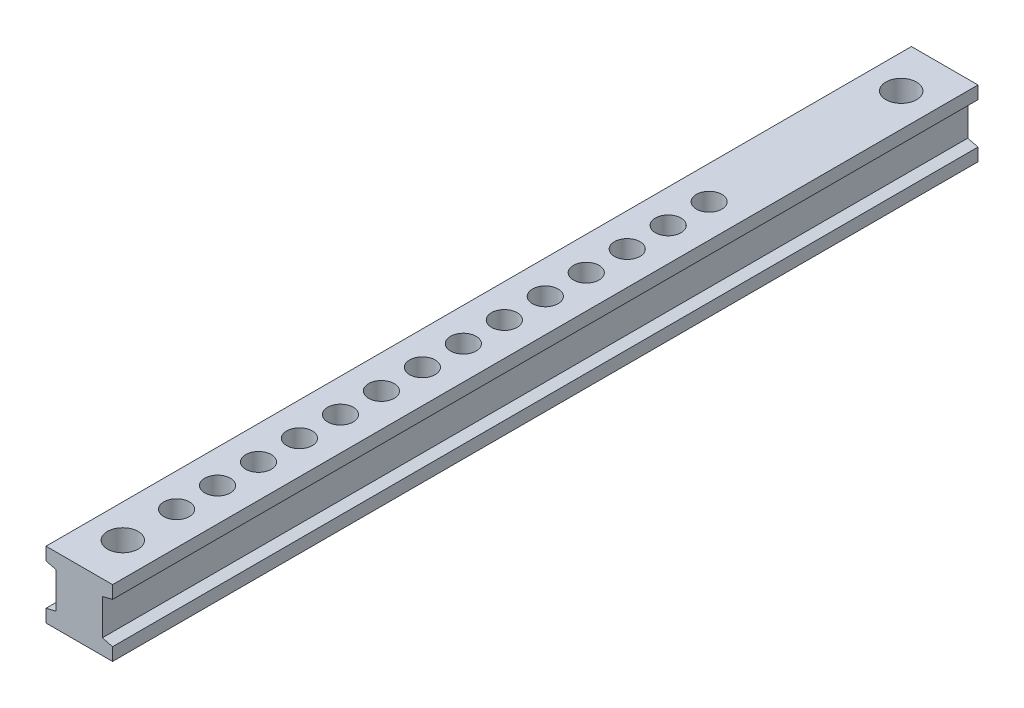
SolidWorks part; units mm, degrees
ref_plane "Front Plane" through (0, 0, 0) normal (0, 0, 1) x (1, 0, 0)
ref_plane "Top Plane" through (0, 0, 0) normal (0, 1, 0) x (1, 0, 0)
ref_plane "Right Plane" through (0, 0, 0) normal (1, 0, 0) x (0, 0, -1)
sketch "Sketch1" plane through (0, 0, 0) normal (0, 0, 1) x (1, 0, 0)
  line L0 (6.5, 4) -> (4.5, 3.5)
  line L1 (-6.5, 6.5) -> (6.5, 6.5)
  line L2 (-6.5, 6.5) -> (-6.5, -6.5)
  line L3 (-6.5, -6.5) -> (6.5, -6.5)
  line L4 (6.5, 6.5) -> (6.5, -6.5)
  line L5 (-6.5, 6.5) -> (6.5, -6.5) construction
  line L6 (-6.5, -6.5) -> (6.5, 6.5) construction
  line L7 (4.5, 3.5) -> (4.5, -3.5)
  line L8 (4.5, -3.5) -> (6.5, -4)
  line L9 (-4.5, 0) -> (4.5, 0) construction
  line L10 (0, -6.5) -> (0, 6.5) construction
  line L11 (6.5, -6.5) -> (-6.5, 6.5) construction
  line L12 (6.5, 6.5) -> (-6.5, -6.5) construction
  line L13 (-4.5, -3.5) -> (-6.5, -4)
  line L14 (-4.5, 3.5) -> (-4.5, -3.5)
  line L15 (-6.5, 6.5) -> (-6.5, -6.5)
  line L16 (-6.5, 4) -> (-4.5, 3.5)
  point P0 (0, 0)
  point P13 (0, 0)
  dimension "D1" = 13
  dimension "D2" = 13
  dimension "D3" = 7
  dimension "D4" = 2
  dimension "D5" = 8
extrude "Boss-Extrude1" add sketch "Sketch1" along normal mid plane 169 contours L2 L16 L14 L13 L3 L4 L8 L7 L0 L1 region at (0, 0, 0)
sketch "Sketch2" plane through (0, 0, 0) normal (0, 1, 0) x (1, 0, 0)
  line L0 (0, 84.5) -> (0, -84.5) construction
  line L1 (-6.5, 84.5) -> (6.5, 84.5) construction
  line L2 (-6.5, -84.5) -> (6.5, -84.5) construction
  line L3 (0, -65.5) -> (0, -57.5) construction
  circle A0 centre (0, 76) radius 3
  circle A1 centre (0, -76) radius 3
  circle A2 centre (0, -65.5) radius 2.5
  circle A3 centre (0, -57.5) radius 2.5
  circle A4 centre (0, -49.5) radius 2.5
  circle A5 centre (0, -41.5) radius 2.5
  circle A6 centre (0, -33.5) radius 2.5
  circle A7 centre (0, -25.5) radius 2.5
  circle A8 centre (0, -17.5) radius 2.5
  circle A9 centre (0, -9.5) radius 2.5
  circle A10 centre (0, -1.5) radius 2.5
  circle A11 centre (0, 6.5) radius 2.5
  circle A12 centre (0, 14.5) radius 2.5
  circle A13 centre (0, 22.5) radius 2.5
  circle A14 centre (0, 30.5) radius 2.5
  circle A15 centre (0, 38.5) radius 2.5
  dimension "D2" = 6
  dimension "D4" = 5
  dimension "D1" = 8.5
  dimension "D3" = 8.5
  dimension "D5" = 19
  dimension "D7" = 8
  dimension "D6" = 14
extrude "Cut-Extrude1" cut sketch "Sketch2" against normal through all both and the other way through all
equation "\"D3@Sketch2\"=\"D1@Sketch2\""
